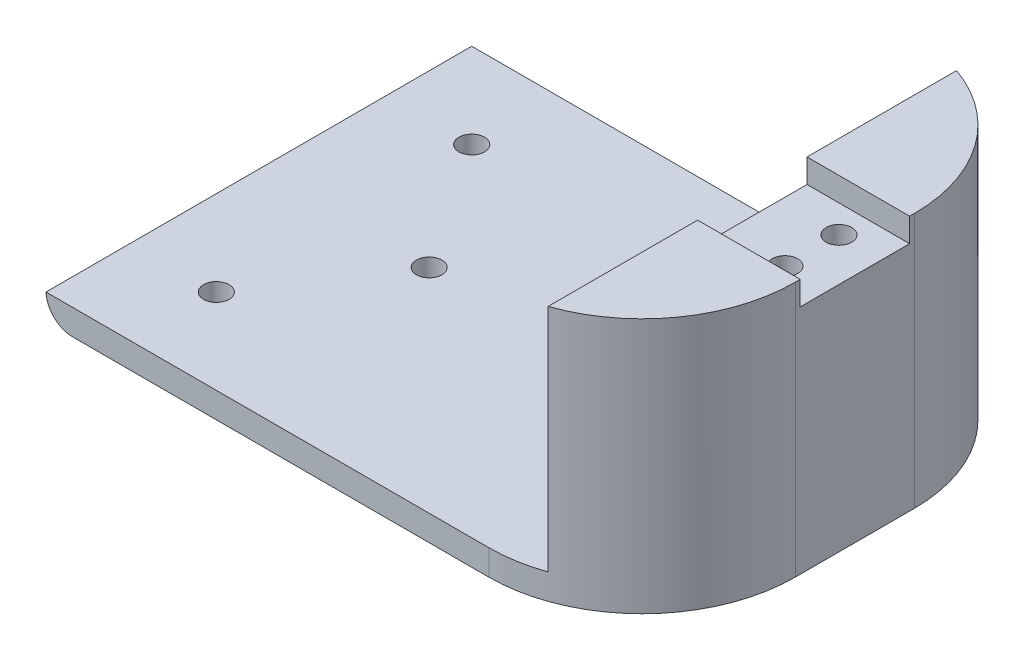
SolidWorks part; units mm, degrees
ref_plane "Front Plane" through (0, 0, 0) normal (0, 0, 1) x (1, 0, 0)
ref_plane "Top Plane" through (0, 0, 0) normal (0, 1, 0) x (1, 0, 0)
ref_plane "Right Plane" through (0, 0, 0) normal (1, 0, 0) x (0, 0, -1)
sketch "ProfileSketch1" plane through (0, 0, 0) normal (0, 0, 1) x (1, 0, 0)
  line L1 (70, 0) -> (70, -3)
  line L2 (70, -3) -> (0, -3)
  line L3 (0, -3) -> (0, 0)
  line L4 (0, 0) -> (57.95, 0)
  line L5 (57.95, 0) -> (57.95, 27)
  line L6 (57.95, 27) -> (70, 27)
  line L7 (70, 27) -> (70, 0)
  dimension "D1" = 70
  dimension "D2" = 3
  dimension "D3" = 27
  dimension "D4" = 12.05
extrude "Boss-Extrude1" add sketch "ProfileSketch1" along normal blind 50
sketch "MountHolesSketch2" plane through (0, 0, 0) normal (0, 1, 0) x (1, 0, 0)
  line L0 (57.95, 0) -> (0, 0) construction
  line L1 (57.95, -50) -> (0, -50) construction
  line L2 (0, -50) -> (0, 0) construction
  line L3 (57.95, -50) -> (57.95, 0) construction
  circle A0 centre (10, -10) radius 1.5
  circle A1 centre (10, -40) radius 1.5
  circle A2 centre (47.95, -25) radius 9
  circle A3 centre (20, -25) radius 1.5
  dimension "D1" = 3
  dimension "D6" = 18
  dimension "D2" = 10
  dimension "D3" = 10
  dimension "D4" = 10
  dimension "D5" = 10
  dimension "D7" = 25
  dimension "D8" = 10
extrude "MountHolesCut-Extrude1" cut sketch "MountHolesSketch2" against normal through all
sketch "MicroSwitchCutSketch3" plane through (0, 27, 0) normal (0, 1, 0) x (1, 0, 0)
  line L0 (57.95, -50) -> (57.95, 0) construction
  line L1 (57.95, -18.575) -> (70, -18.575)
  line L2 (57.95, -18.575) -> (57.95, -31.425)
  line L3 (57.95, -31.425) -> (70, -31.425)
  line L4 (70, -18.575) -> (70, -31.425)
  line L5 (70, -50) -> (70, 0) construction
  line L6 (70, 0) -> (57.95, 0) construction
  dimension "D1" = 12.85
  dimension "D2" = 18.575
extrude "MicroSwitchCut-Extrude2" cut sketch "MicroSwitchCutSketch3" against normal blind 2.8
sketch "MicroSwitchMountingHolesSketch4" plane through (0, 24.2, 0) normal (0, 1, 0) x (1, 0, 0)
  line L0 (57.95, -31.425) -> (70, -31.425) construction
  line L1 (70, -18.575) -> (57.95, -18.575) construction
  line L2 (57.95, -50) -> (57.95, 0) construction
  circle A0 centre (64.95, -28.175) radius 1.5
  circle A1 centre (64.95, -21.825) radius 1.5
  dimension "D4" = 3
  dimension "D1" = 3.25
  dimension "D2" = 3.25
  dimension "D3" = 7
extrude "MicroSwitchMountingHolesCut-Extrude3" cut sketch "MicroSwitchMountingHolesSketch4" against normal blind 3
fillet "RailEdgeFillet1" radius 3.125 1 edges at (0, -3, 25)
fillet "FrontEdgeFillet1" radius 18 2 edges at (70, 12, 0) (70, 12, 50)
equation "\"M3ScrewDiameter\"= 3mm"
equation "\"D1@MountHolesSketch2\" = \"M3ScrewDiameter\""
equation "\"YAxisMicroSwitchBlockWidth\"= 50mm"
equation "\"MicroSwitchLength\"= 12.85mm"
equation "\"MicroSwitchTerminalHeight\"= 3.5mm"
equation "\"MicroSwitchDepth\"= 2.8mm"
equation "\"MicroSwitchMountHoleOffsetFromSide\"= 3.25mm"
equation "\"MicroSwitchMountHoleOffsetFromBottom\"= 1.5mm"
equation "\"MicroSwitchExtraMountingHeight\"= 2mm"
equation "\"D1@Boss-Extrude1\"=\"YAxisMicroSwitchBlockWidth\""
equation "\"D7@MountHolesSketch2\" = \"YAxisMicroSwitchBlockWidth\" / 2"
equation "\"D1@MicroSwitchCutSketch3\" = \"MicroSwitchLength\""
equation "\"D2@MicroSwitchCutSketch3\" = \"YAxisMicroSwitchBlockWidth\" / 2 - \"MicroSwitchLength\" / 2"
equation "\"D1@MicroSwitchCut-Extrude2\" = \"MicroSwitchDepth\""
equation "\"D1@MicroSwitchMountingHolesSketch4\" = \"MicroSwitchMountHoleOffsetFromSide\""
equation "\"D2@MicroSwitchMountingHolesSketch4\" = \"MicroSwitchMountHoleOffsetFromSide\""
equation "\"D3@MicroSwitchMountingHolesSketch4\"=\"MicroSwitchExtraMountingHeight\" + \"MicroSwitchTerminalHeight\" + \"MicroSwitchMountHoleOffsetFromBottom\""
equation "\"M3HeatInsertHoleDiameter\"= 3mm'Spec"
equation "\"D4@MicroSwitchMountingHolesSketch4\" = \"M3HeatInsertHoleDiameter\""
equation "\"M3HeatInsertHoleDepth\"= 4mm"
equation "\"YAxisMicroSwitchMountingBlockHeight\"= 27mm"
equation "\"YAxisMicroSwitchSupportHeight\"= 3mm"
equation "\"D2@ProfileSketch1\"=\"YAxisMicroSwitchSupportHeight\""
equation "\"D3@ProfileSketch1\"=\"YAxisMicroSwitchMountingBlockHeight\""
equation "\"D4@ProfileSketch1\"=\"MicroSwitchExtraMountingHeight\" + \"MicroSwitchTerminalHeight\" + 6.55mm"
equation "\"MicroSwitchHeight\"= 6.55mm"
equation "\"M2HeatInsertDepth\"=3"
equation "\"D1@MicroSwitchMountingHolesCut-Extrude3\" = \"M2HeatInsertDepth\""
equation "\"MicroSwitchCableClampHoleDiameter\"=18"
